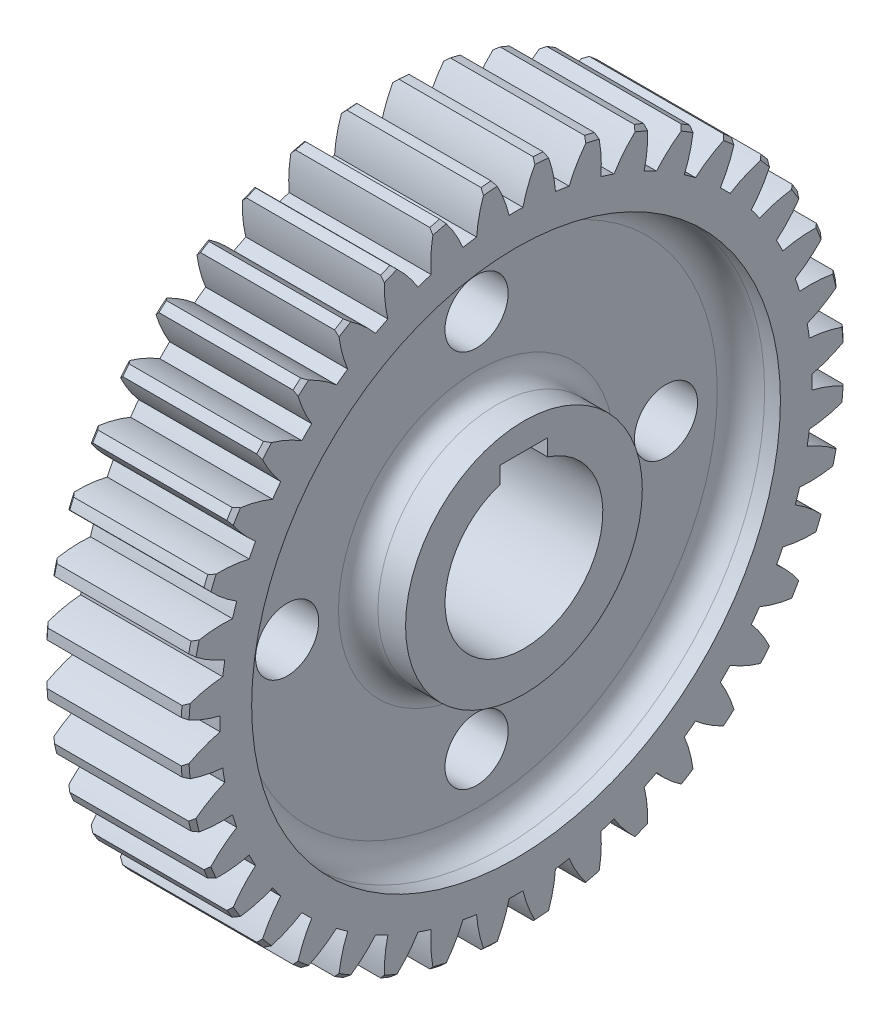
SolidWorks part; units mm, degrees
ref_plane "Plane1" through (0, 0, 0) normal (0, 0, 1) x (1, 0, 0)
ref_plane "Plane2" through (0, 0, 0) normal (0, 1, 0) x (1, 0, 0)
ref_plane "Plane3" through (0, 0, 0) normal (1, 0, 0) x (0, 0, -1)
sketch "HoldingSke" plane through (0, 0, 0) normal (0, 1, 0) x (1, 0, 0)
  line L0 (0, 0) -> (0.1915, -0.1607)
  line L1 (-15, 0) -> (100, 0) construction
  line L2 (0, 0) -> (-2.1039, 2.3779)
  line L3 (0, 0) -> (-11.863, 4.5341)
  line L4 (0, 0) -> (6.6156, 5.5511)
  line L5 (0, 0) -> (-37.4781, -13.9782)
  line L6 (0, 0) -> (-29.8427, -20.1349)
  line L7 (-2.1039, 2.3779) -> (6.5061, 41.4403)
  line L8 (-76.2, 54.61) -> (-72.9, 54.61)
  line L9 (-71.009, 38.7566) -> (-53.1078, 45.2721)
  line L10 (-76.2, 71.12) -> (104.1128, 71.12)
  line L11 (0, 0) -> (-36, 0)
  line L12 (-76.2, 101.6) -> (-76.073, 101.6)
  line L13 (24.9733, 27.94) -> (52.9518, 28.4284)
  line L14 (24.9733, 27.94) -> (24.9743, 27.94)
  line L15 (24.9733, 27.94) -> (100.4006, 29.5858)
  line L16 (-63.627, -4) -> (-12.827, -4)
  circle A0 centre (0, 0) radius 20
  circle A1 centre (0, 0) radius 30
  circle A2 centre (0, 0) radius 30
  circle A3 centre (0, 0) radius 20
  dimension "MHD" = 60
  dimension "Hub_dia" = 60
  dimension "Bore" = 40
  dimension "MBD" = 40
  dimension "Num_teeth" = 40
  dimension "Pitch_radius" = 180.3128
  dimension "Pitch" = 0.25
  dimension "Width" = 36
  dimension "Overall_len" = 40
  dimension "Show_teeth" = 40
  dimension "Thickness" = 36
  dimension "OAL" = 40.0001
  dimension "T_dim" = 3.3
  dimension "Ap" = 20
  dimension "H" = 19.05
  dimension "Backlash" = 0.127
  dimension "Addendum_fac" = 1
  dimension "Dedendum_fac" = 1.25
  dimension "Clearance_fac" = 0.25
  dimension "Dedendum_add" = 0.001
  dimension "Module" = 4
sketch "BasProSke" plane through (0, 0, 0) normal (0, 1, 0) x (1, 0, 0)
  line L0 (-10, 0) -> (60, 0) construction
  line L1 (0, 0) -> (0, 84)
  line L2 (0, 0) -> (36, 0)
  line L3 (36, 0) -> (36, 84)
  line L4 (36, 84) -> (0, 84)
  dimension "Diameter" = 168
  dimension "Thickness" = 36
revolve "Base-Revolve" add sketch "BasProSke" angle 360 about L0
sketch "TooCutSke" plane through (0, 0, 0) normal (1, 0, 0) x (0, 0, -1)
  line L1 (0, 0) -> (0, 107) construction
  line L2 (0, 0) -> (-3.363, 79.9293) construction
  line L3 (0, 0) -> (-12.5451, 159.4006) construction
  line L4 (-3.363, 79.9293) -> (-6.2725, 79.7003) construction
  arc A0 (1.7544, 74.9785) -> (-1.7544, 74.9785) centre (0, 0) ccw
  arc A1 (5.3295, 83.8562) -> (-5.3295, 83.8562) centre (0, 0) ccw
  circle A2 centre (0, 0) radius 80 construction
  circle A3 centre (0, 0) radius 75.1754 construction
  arc A4 (-1.7544, 74.9785) -> (-5.3295, 83.8562) centre (-32.8916, 67.598) ccw
  arc A5 (5.3295, 83.8562) -> (1.7544, 74.9785) centre (32.8916, 67.598) ccw
  dimension "Root_dia" = 149.998
  dimension "Overcut_dia" = 168.0508
  dimension "Pitch_dia" = 160
  dimension "Base_dia" = 150.3508
  dimension "Flank_rad" = 32
  dimension "Half_ang" = 4.5
  dimension "Half_CT" = 2.9185
extrude "ToothCut" cut sketch "TooCutSke" along normal through all
fillet "Breaks" [suppressed] radius 0.08 tangent propagation no
fillet "RootFillets" [suppressed] radius 1.001
pattern_circular "TeethCuts" count 40 every 9 about axis through (-10, 0, 0) along (1, 0, 0) of "ToothCut", "RootFillets", "Breaks"
sketch "HubNeaOneSke" plane through (0, 0, 0) normal (-1, 0, 0) x (0, 0, 1)
  circle A0 centre (0, 0) radius 30
  dimension "Diameter" = 60
extrude "HubNearOne" [suppressed] add sketch "HubNeaOneSke" along normal blind 4.0001
sketch "HubNeaBotSke" plane through (0, 0, 0) normal (-1, 0, 0) x (0, 0, 1)
  circle A0 centre (0, 0) radius 30
  dimension "Diameter" = 60
extrude "HubNearBoth" add sketch "HubNeaBotSke" along normal blind 2
ref_plane "FarPln" through (36, 0, 0) normal (1, 0, 0) x (0, 0, -1)
sketch "HubFarSke" plane through (36, 0, 0) normal (1, 0, 0) x (0, 0, -1)
  circle A0 centre (0, 0) radius 30
  dimension "Diameter" = 60
extrude "HubFar" add sketch "HubFarSke" along normal blind 2
sketch "BorSke" plane through (0, 0, 0) normal (1, 0, 0) x (0, 0, -1)
  circle A0 centre (0, 0) radius 20
  dimension "Diameter" = 40
extrude "Bore" cut sketch "BorSke" along normal mid plane 80.0001
sketch "KeySke" plane through (0, 0, 0) normal (1, 0, 0) x (0, 0, -1)
  line L0 (-6, 0) -> (-6, 23.3)
  line L1 (-6, 23.3) -> (6, 23.3)
  line L2 (6, 23.3) -> (6, 0)
  line L3 (0, 0) -> (0, 34) construction
  line L4 (-6, 0) -> (6, 0)
  dimension "Offset" = 23.3
  dimension "Width" = 12
extrude "Keyway" cut sketch "KeySke" along normal mid plane 80.0001
pattern_circular "Keyway2" [suppressed] count 2 every 90 about axis through (-10, 0, 0) along (1, 0, 0)
sketch "草图3" plane through (0, 0, 0) normal (-1, 0, 0) x (0, 0, 1)
  circle A0 centre (0, 0) radius 30
  circle A1 centre (0, 0) radius 67
extrude "切除-拉伸1" cut sketch "草图3" against normal blind 10
fillet "圆角1" radius 6 1 edges at (10, 0, 67) type face fillet first side face at (10, 0, 30) second side face at (10, 0, 67)
fillet "圆角2" radius 5 1 edges at (10, 0, 30) type face fillet first side face at (10, 0, 61) second side face at (-2, 0, 30)
ref_plane "基准面1" through (18, 0, 0) normal (1, 0, 0) x (0, 0, -1)
mirror "镜向3" about plane through (18, 0, 0) normal (1, 0, 0) of "切除-拉伸1"
fillet "圆角3" radius 5 1 edges at (26, 0, 30) type face fillet first side face at (26, 0, 67) second side face at (38, 0, -30)
fillet "圆角4" radius 6 1 edges at (26, 0, 67) type face fillet first side face at (26, 0, -35) second side face at (26, 0, 67)
sketch "草图5" plane through (10, 0, 0) normal (-1, 0, 0) x (0, 0, 1)
  circle A0 centre (0, 48) radius 8
  circle A1 centre (0, -48) radius 8
  circle A2 centre (48, 0) radius 8
  circle A3 centre (-48, 0) radius 8
extrude "切除-拉伸2" cut sketch "草图5" against normal blind 26
sketch "草图7" plane through (0, 0, 0) normal (0, 0, 1) x (1, 0, 0)
  line L1 (-0.9219, 85.3238) -> (1, 84)
  line L2 (1, 84) -> (0, 83)
  line L3 (0, 83) -> (-0.9219, 85.3238)
  line L4 (36, 74.3298) -> (36, 83.631) construction
  line L5 (38.6831, 85.3238) -> (36, 83)
  line L6 (38.6831, 85.3238) -> (35, 84)
  line L7 (35, 84) -> (36, 83)
  point P0 (0, 83)
  point P1 (1, 84)
  point P2 (-0.9219, 85.3238)
  point P5 (36, 83)
  point P7 (35, 84)
  point P10 (38.6831, 85.3238)
ref_axis "基准轴1" through (38, 0, 0) along (-1, 0, 0)
revolve "切除-旋转1" cut sketch "草图7" angle 360 about axis through (38, 0, 0) along (-1, 0, 0)
equation "' \"Module@HoldingSke\" = 6.35"
equation "' \"Num_teeth@HoldingSke\" = 12"
equation "' \"Ap@HoldingSke\" =  20"
equation "' \"Width@HoldingSke\" = 0.5 * 25.4"
equation "' \"Hub_dia@HoldingSke\"= 1 * 25.4"
equation "' \"Overall_len@HoldingSke\" = 1.0 * 25.4"
equation "' \"Bore@HoldingSke\" = 0.75 * 25.4"
equation "' \"T_dim@HoldingSke\" = 0.1 * 25.4"
equation "' \"Width@KeySke\" = 0.25 * 25.4"
equation "' \"Show_teeth@HoldingSke\" = 13"
equation "' \"Backlash@HoldingSke\" = 0.009 * 25.4"
equation "' \"Addendum_fac@HoldingSke\" = 1.0"
equation "' \"Dedendum_fac@HoldingSke\" = 1.25"
equation "' \"Dedendum_add@HoldingSke\" = 0.00005 * 25.4"
equation "' \"Clearance_fac@HoldingSke\" = 0.25"
equation "\"Pitch@HoldingSke\" = 1 / \"Module@HoldingSke\""
equation "\"Overcut_dia@TooCutSke\" = (\"Num_teeth@HoldingSke\" + 2 * \"Addendum_fac@HoldingSke\") / \"Pitch@HoldingSke\" + 0.002 * 25.4"
equation "\"Pitch_dia@TooCutSke\" = \"Num_teeth@HoldingSke\" / \"Pitch@HoldingSke\""
equation "\"Base_dia@TooCutSke\" = \"Num_teeth@HoldingSke\" / \"Pitch@HoldingSke\" * cos((\"Ap@HoldingSke\"  * 3.14159265 / 180))"
equation "\"Root_dia@TooCutSke\" = (\"Num_teeth@HoldingSke\" + 2) / \"Pitch@HoldingSke\" - 2 * (\"Addendum_fac@HoldingSke\" + \"Dedendum_fac@HoldingSke\") / \"Pitch@HoldingSke\" - \"Dedendum_add@HoldingSke\" * 2"
equation "\"Half_ang@TooCutSke\" = 180 / \"Num_teeth@HoldingSke\""
equation "\"Half_CT@TooCutSke\" = \"Num_teeth@HoldingSke\" / \"Pitch@HoldingSke\" * sin((3.14159265 / 2 / \"Num_teeth@HoldingSke\")) / 2 - 7 * \"Backlash@HoldingSke\" / 4"
equation "\"Flank_rad@TooCutSke\" = \"Num_teeth@HoldingSke\" / \"Pitch@HoldingSke\" / 5"
equation "\"Radius@RootFillets\" = \"Clearance_fac@HoldingSke\" / \"Pitch@HoldingSke\" + \"Dedendum_add@HoldingSke\""
equation "\"Break_rad@Breaks\" = 0.02 / \"Pitch@HoldingSke\""
equation "\"Thickness@HoldingSke\" = \"Width@HoldingSke\""
equation "\"OAL@HoldingSke\" = \"Thickness@HoldingSke\""
equation "\"MHD@HoldingSke\" = (\"Num_teeth@HoldingSke\" + 2) / \"Pitch@HoldingSke\" - 2 * (\"Addendum_fac@HoldingSke\" + \"Dedendum_fac@HoldingSke\")  / \"Pitch@HoldingSke\" - \"Dedendum_add@HoldingSke\" * 2"
equation "\"MBD@HoldingSke\" = (\"Num_teeth@HoldingSke\" + 2) / \"Pitch@HoldingSke\" - 2 * (\"Addendum_fac@HoldingSke\" + \"Dedendum_fac@HoldingSke\")  / \"Pitch@HoldingSke\" - \"Dedendum_add@HoldingSke\" * 2 - 0.002 * 25.4"
equation "\"MHD@HoldingSke\" = ((sgn( \"MHD@HoldingSke\" - \"Hub_dia@HoldingSke\" )-1)*( \"MHD@HoldingSke\" - \"Hub_dia@HoldingSke\" ))/-2+ \"Hub_dia@HoldingSke\""
equation "\"MBD@HoldingSke\" = ((sgn( \"MBD@HoldingSke\" - \"Bore@HoldingSke\" )-1)*( \"MBD@HoldingSke\" - \"Bore@HoldingSke\" ))/-2+ \"Bore@HoldingSke\""
equation "\"OAL@HoldingSke\" = ((sgn( \"OAL@HoldingSke\" - \"Overall_len@HoldingSke\" )+1)*( \"OAL@HoldingSke\" - \"Overall_len@HoldingSke\" ))/2 + \"Overall_len@HoldingSke\" + 0.000002 * 25.4"
equation "\"Num_teeth@TeethCuts\" = int( \"Show_teeth@HoldingSke\" ) + 1"
equation "\"Num_teeth@TeethCuts\" = ((sgn( \"Num_teeth@TeethCuts\" - \"Num_teeth@HoldingSke\" )-1)*( \"Num_teeth@TeethCuts\" - \"Num_teeth@HoldingSke\" ))/-2+ \"Num_teeth@HoldingSke\""
equation "\"Num_teeth@TeethCuts\" = ((sgn( \"Num_teeth@TeethCuts\" - 2.0)+1)*( \"Num_teeth@TeethCuts\" - 2.0))/2 +2.0"
equation "\"Angle@TeethCuts\" = 360.0 / \"Num_teeth@HoldingSke\""
equation "\"Diameter@BasProSke\" = (\"Num_teeth@HoldingSke\" + 2 * \"Addendum_fac@HoldingSke\") / \"Pitch@HoldingSke\""
equation "\"Thickness@BasProSke\"  = \"Thickness@HoldingSke\""
equation "' \"Fillet_rad@BasProSke\" =  \"Thickness@HoldingSke\" * 0.05"
equation "\"MHD@HoldingSke\" = ((sgn( \"MHD@HoldingSke\" - \"Root_dia@TooCutSke\" )-1)*( \"MHD@HoldingSke\" - \"Root_dia@TooCutSke\" ))/-2+ \"Root_dia@TooCutSke\""
equation "\"Diameter@HubNeaOneSke\" = \"MHD@HoldingSke\""
equation "\"Length@HubNearOne\" = \"OAL@HoldingSke\" - \"Thickness@BasProSke\""
equation "\"Diameter@HubNeaBotSke\" = \"MHD@HoldingSke\""
equation "\"Length@HubNearBoth\" = ( \"OAL@HoldingSke\" - \"Thickness@BasProSke\" ) / 2.0"
equation "\"Thickness@FarPln\" = \"Thickness@BasProSke\""
equation "\"Diameter@HubFarSke\" = \"MHD@HoldingSke\""
equation "\"Length@HubFar\" = ( \"OAL@HoldingSke\" - \"Thickness@BasProSke\" ) / 2.0"
equation "\"Diameter@BorSke\" = \"MBD@HoldingSke\""
equation "\"D1@Bore\" = \"OAL@HoldingSke\" * 2.0"
equation "\"D1@Keyway\" = \"OAL@HoldingSke\" * 2.0"
equation "\"Offset@KeySke\" = \"T_dim@HoldingSke\" + \"MBD@HoldingSke\" / 2.0"
